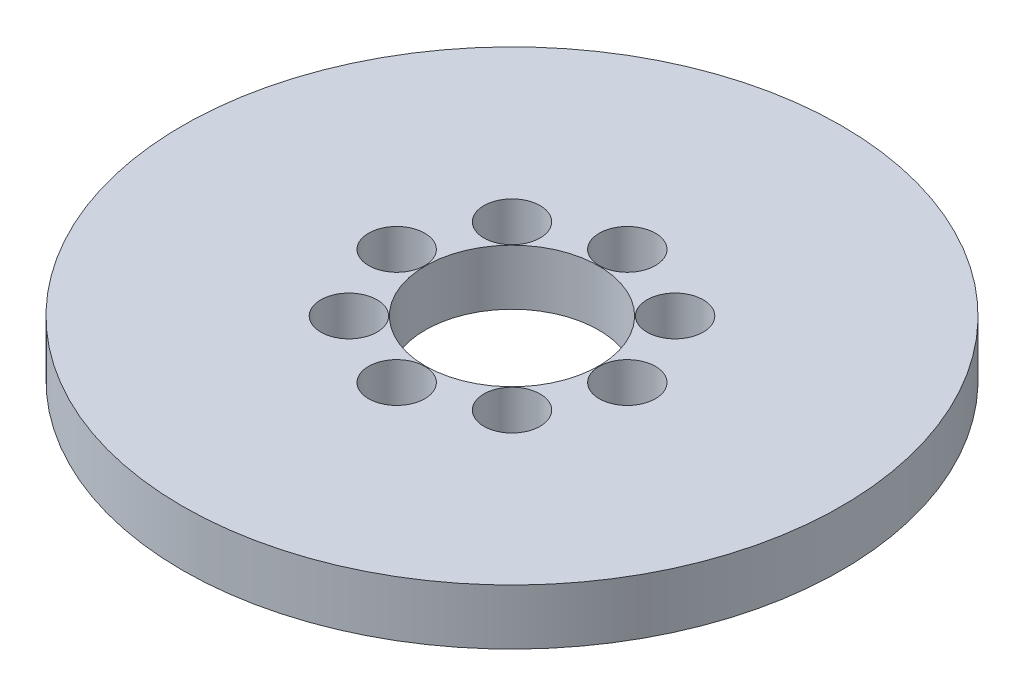
SolidWorks part; units mm, degrees
ref_plane "Front Plane" through (0, 0, 0) normal (0, 0, 1) x (1, 0, 0)
ref_plane "Top Plane" through (0, 0, 0) normal (0, 1, 0) x (1, 0, 0)
ref_plane "Right Plane" through (0, 0, 0) normal (1, 0, 0) x (0, 0, -1)
sketch "Sketch1" plane through (0, 0, 0) normal (0, 1, 0) x (1, 0, 0)
  circle A0 centre (0, 0) radius 95
  dimension "FLANGE_OD" = 190
extrude "Boss-Extrude1" add sketch "Sketch1" along normal blind 16
sketch "Sketch2" plane through (0, 0, 0) normal (0, 1, 0) x (1, 0, 0)
  circle A0 centre (0, 0) radius 25
  dimension "BORE_D" = 50
extrude "Cut-Extrude1" cut sketch "Sketch2" along normal through all
sketch "Sketch3" plane through (0, 16, 0) normal (0, 1, 0) x (1, 0, 0)
  circle A0 centre (0, 0) radius 33.2437 construction
  circle A1 centre (-33.2437, 0) radius 8.0989
  dimension "BOLT_D" = 16.1978
  dimension "BOLT_PCD" = 66.4873
extrude "Cut-Extrude2" cut sketch "Sketch3" against normal blind 14.631
pattern_circular "CirPattern1" count 8 over 360 about axis through (0, 0, 0) along (0, 1, 0) of "Cut-Extrude2"
